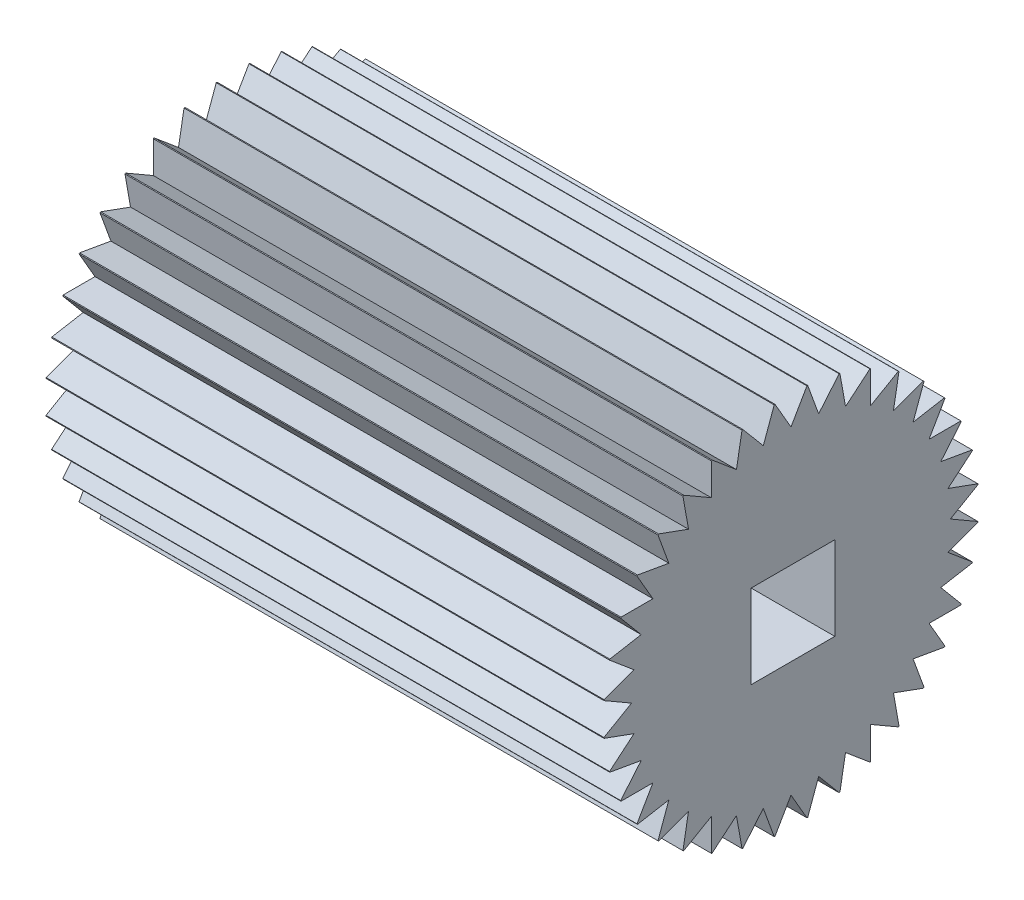
SolidWorks part; units mm, degrees
ref_plane "Front Plane" through (0, 0, 0) normal (0, 0, 1) x (1, 0, 0)
ref_plane "Top Plane" through (0, 0, 0) normal (0, 1, 0) x (1, 0, 0)
ref_plane "Right Plane" through (0, 0, 0) normal (1, 0, 0) x (0, 0, -1)
sketch "Sketch1" plane through (0, 0, 0) normal (1, 0, 0) x (0, 0, -1)
  line L101 (0, 0) -> (0, 17.584) construction
  line L102 (-1, 11.7321) -> (0, 10)
  line L105 (1.0524, 11.7275) -> (1.7365, 9.8481)
  line L106 (3.0221, 11.3802) -> (1.7365, 9.8481)
  line L111 (5, 10.6603) -> (5, 8.6603)
  line L112 (6.7321, 9.6603) -> (5, 8.6603)
  line L113 (6.7752, 9.6301) -> (6.4279, 7.6604)
  line L114 (8.3073, 8.3445) -> (6.4279, 7.6604)
  line L115 (8.3445, 8.3073) -> (7.6604, 6.4279)
  line L116 (9.6301, 6.7752) -> (7.6604, 6.4279)
  line L117 (9.6603, 6.7321) -> (8.6603, 5)
  line L118 (10.6603, 5) -> (8.6603, 5)
  line L119 (10.6825, 4.9523) -> (9.3969, 3.4202)
  line L120 (11.3665, 3.0729) -> (9.3969, 3.4202)
  line L121 (11.3802, 3.0221) -> (9.8481, 1.7365)
  line L122 (11.7275, 1.0524) -> (9.8481, 1.7365)
  line L123 (11.7321, 1) -> (10, 0)
  line L124 (11.7321, -1) -> (10, 0)
  line L125 (11.7275, -1.0524) -> (9.8481, -1.7365)
  line L126 (11.3802, -3.0221) -> (9.8481, -1.7365)
  line L127 (1, 11.7321) -> (0, 10)
  line L128 (11.3665, -3.0729) -> (9.3969, -3.4202)
  line L129 (10.6825, -4.9523) -> (9.3969, -3.4202)
  line L130 (10.6603, -5) -> (8.6603, -5)
  line L131 (9.6603, -6.7321) -> (8.6603, -5)
  line L132 (9.6301, -6.7752) -> (7.6604, -6.4279)
  line L133 (8.3445, -8.3073) -> (7.6604, -6.4279)
  line L134 (8.3073, -8.3445) -> (6.4279, -7.6604)
  line L135 (6.7752, -9.6301) -> (6.4279, -7.6604)
  line L136 (6.7321, -9.6603) -> (5, -8.6603)
  line L137 (5, -10.6603) -> (5, -8.6603)
  line L138 (4.9523, -10.6825) -> (3.4202, -9.3969)
  line L139 (3.0729, -11.3665) -> (3.4202, -9.3969)
  line L140 (3.0221, -11.3802) -> (1.7365, -9.8481)
  line L141 (1.0524, -11.7275) -> (1.7365, -9.8481)
  line L142 (1, -11.7321) -> (0, -10)
  line L143 (-1, -11.7321) -> (0, -10)
  line L144 (-1.0524, -11.7275) -> (-1.7365, -9.8481)
  line L145 (-3.0221, -11.3802) -> (-1.7365, -9.8481)
  line L146 (-3.0729, -11.3665) -> (-3.4202, -9.3969)
  line L147 (-4.9523, -10.6825) -> (-3.4202, -9.3969)
  line L148 (-5, -10.6603) -> (-5, -8.6603)
  line L149 (-6.7321, -9.6603) -> (-5, -8.6603)
  line L150 (-6.7752, -9.6301) -> (-6.4279, -7.6604)
  line L151 (-8.3073, -8.3445) -> (-6.4279, -7.6604)
  line L152 (-8.3445, -8.3073) -> (-7.6604, -6.4279)
  line L153 (-9.6301, -6.7752) -> (-7.6604, -6.4279)
  line L154 (-9.6603, -6.7321) -> (-8.6603, -5)
  line L155 (-10.6603, -5) -> (-8.6603, -5)
  line L156 (-10.6825, -4.9523) -> (-9.3969, -3.4202)
  line L157 (-11.3665, -3.0729) -> (-9.3969, -3.4202)
  line L158 (-11.3802, -3.0221) -> (-9.8481, -1.7365)
  line L159 (-11.7275, -1.0524) -> (-9.8481, -1.7365)
  line L160 (-11.7321, -1) -> (-10, 0)
  line L161 (-11.7321, 1) -> (-10, 0)
  line L162 (-11.7275, 1.0524) -> (-9.8481, 1.7365)
  line L163 (-11.3802, 3.0221) -> (-9.8481, 1.7365)
  line L164 (-11.3665, 3.0729) -> (-9.3969, 3.4202)
  line L165 (-10.6825, 4.9523) -> (-9.3969, 3.4202)
  line L166 (-10.6603, 5) -> (-8.6603, 5)
  line L167 (-9.6603, 6.7321) -> (-8.6603, 5)
  line L168 (-9.6301, 6.7752) -> (-7.6604, 6.4279)
  line L169 (-8.3445, 8.3073) -> (-7.6604, 6.4279)
  line L170 (-8.3073, 8.3445) -> (-6.4279, 7.6604)
  line L171 (-6.7752, 9.6301) -> (-6.4279, 7.6604)
  line L172 (-6.7321, 9.6603) -> (-5, 8.6603)
  line L173 (-5, 10.6603) -> (-5, 8.6603)
  line L174 (-4.9523, 10.6825) -> (-3.4202, 9.3969)
  line L175 (-3.0729, 11.3665) -> (-3.4202, 9.3969)
  line L176 (-3.0221, 11.3802) -> (-1.7365, 9.8481)
  line L177 (-1.0524, 11.7275) -> (-1.7365, 9.8481)
  line L178 (3.0729, 11.3665) -> (3.4202, 9.3969)
  line L179 (4.9523, 10.6825) -> (3.4202, 9.3969)
  arc A53 (1.0524, 11.7275) -> (1, 11.7321) centre (0, 0) ccw
  arc A55 (5, 10.6603) -> (4.9523, 10.6825) centre (0, 0) ccw
  arc A56 (6.7752, 9.6301) -> (6.7321, 9.6603) centre (0, 0) ccw
  arc A57 (8.3445, 8.3073) -> (8.3073, 8.3445) centre (0, 0) ccw
  arc A58 (9.6603, 6.7321) -> (9.6301, 6.7752) centre (0, 0) ccw
  arc A59 (10.6825, 4.9523) -> (10.6603, 5) centre (0, 0) ccw
  arc A60 (11.3802, 3.0221) -> (11.3665, 3.0729) centre (0, 0) ccw
  arc A61 (11.7321, 1) -> (11.7275, 1.0524) centre (0, 0) ccw
  arc A62 (11.7275, -1.0524) -> (11.7321, -1) centre (0, 0) ccw
  arc A63 (11.3665, -3.0729) -> (11.3802, -3.0221) centre (0, 0) ccw
  arc A64 (10.6603, -5) -> (10.6825, -4.9523) centre (0, 0) ccw
  arc A65 (9.6301, -6.7752) -> (9.6603, -6.7321) centre (0, 0) ccw
  arc A66 (8.3073, -8.3445) -> (8.3445, -8.3073) centre (0, 0) ccw
  arc A67 (6.7321, -9.6603) -> (6.7752, -9.6301) centre (0, 0) ccw
  arc A68 (4.9523, -10.6825) -> (5, -10.6603) centre (0, 0) ccw
  arc A69 (3.0221, -11.3802) -> (3.0729, -11.3665) centre (0, 0) ccw
  arc A70 (1, -11.7321) -> (1.0524, -11.7275) centre (0, 0) ccw
  arc A71 (-1.0524, -11.7275) -> (-1, -11.7321) centre (0, 0) ccw
  arc A72 (-3.0729, -11.3665) -> (-3.0221, -11.3802) centre (0, 0) ccw
  arc A73 (-5, -10.6603) -> (-4.9523, -10.6825) centre (0, 0) ccw
  arc A74 (-6.7752, -9.6301) -> (-6.7321, -9.6603) centre (0, 0) ccw
  arc A75 (-8.3445, -8.3073) -> (-8.3073, -8.3445) centre (0, 0) ccw
  arc A76 (-9.6603, -6.7321) -> (-9.6301, -6.7752) centre (0, 0) ccw
  arc A77 (-10.6825, -4.9523) -> (-10.6603, -5) centre (0, 0) ccw
  arc A78 (-11.3802, -3.0221) -> (-11.3665, -3.0729) centre (0, 0) ccw
  arc A79 (-11.7321, -1) -> (-11.7275, -1.0524) centre (0, 0) ccw
  arc A80 (-11.7275, 1.0524) -> (-11.7321, 1) centre (0, 0) ccw
  arc A81 (-11.3665, 3.0729) -> (-11.3802, 3.0221) centre (0, 0) ccw
  arc A82 (-10.6603, 5) -> (-10.6825, 4.9523) centre (0, 0) ccw
  arc A83 (-9.6301, 6.7752) -> (-9.6603, 6.7321) centre (0, 0) ccw
  arc A84 (-8.3073, 8.3445) -> (-8.3445, 8.3073) centre (0, 0) ccw
  arc A85 (-6.7321, 9.6603) -> (-6.7752, 9.6301) centre (0, 0) ccw
  arc A86 (-4.9523, 10.6825) -> (-5, 10.6603) centre (0, 0) ccw
  arc A87 (-3.0221, 11.3802) -> (-3.0729, 11.3665) centre (0, 0) ccw
  arc A88 (-1, 11.7321) -> (-1.0524, 11.7275) centre (0, 0) ccw
  arc A89 (3.0729, 11.3665) -> (3.0221, 11.3802) centre (0, 0) ccw
  point P12 (0, 0)
  point P16 (0, 0)
  point P17 (0, 0)
  point P156 (0, 0)
  dimension "D1" = 30
  dimension "D2" = 2
  dimension "D3" = 10
  dimension "D4" = 3
extrude "Boss-Extrude1" add sketch "Sketch1" along normal blind 35
sketch "Sketch3" plane through (35, 0, 0) normal (1, 0, 0) x (0, 0, -1)
  line L1 (2.75, 2.5) -> (-2.5, 2.5)
  line L2 (2.75, 2.5) -> (2.75, -2.75)
  line L3 (2.75, -2.75) -> (-2.5, -2.75)
  line L4 (-2.5, 2.5) -> (-2.5, -2.75)
  dimension "D1" = 5.25
  dimension "D2" = 5.25
  dimension "D3" = 2.75
  dimension "D4" = 2.75
extrude "Cut-Extrude2" cut sketch "Sketch3" against normal blind 10.2
sketch "Sketch4" plane through (35, 0, 0) normal (1, 0, 0) x (0, 0, -1)
  circle A0 centre (4.05, 0) radius 0.4
  circle A1 centre (0, -4.05) radius 0.4
  circle A2 centre (-4.05, 0) radius 0.4
  circle A3 centre (0, 4.05) radius 0.4
  point P12 (0, 0)
  dimension "D1" = 0.8
  dimension "D2" = 4.05
  dimension "D3" = 4
extrude "Cut-Extrude3" cut sketch "Sketch3<2>" along normal blind 10 from surface starting at face at (0, 0, 0)
sketch "Sketch3<2>" plane through (35, 0, 0) normal (1, 0, 0) x (0, 0, -1) same geometry as "Sketch3"
